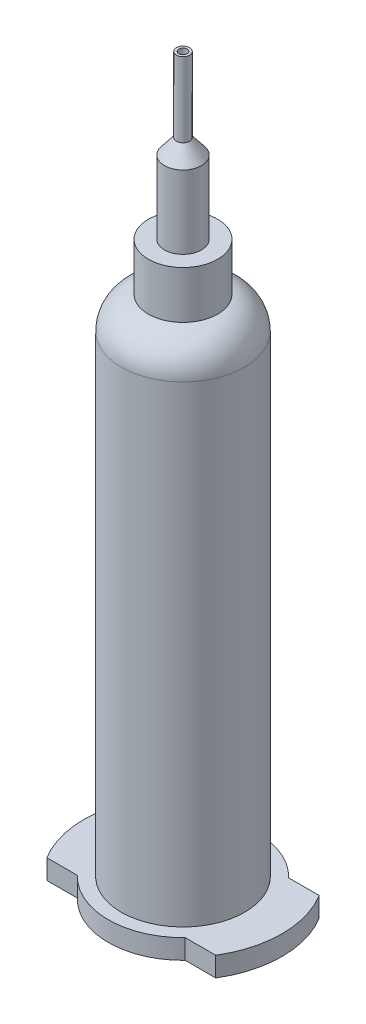
SolidWorks part; units mm, degrees
ref_plane "Front Plane" through (0, 0, 0) normal (0, 0, 1) x (1, 0, 0)
ref_plane "Top Plane" through (0, 0, 0) normal (0, 1, 0) x (1, 0, 0)
ref_plane "Right Plane" through (0, 0, 0) normal (1, 0, 0) x (0, 0, -1)
ref_axis "Axis1" through (-33.0333, 0, 0) along (1, 0, 0)
ref_axis "Axis2" through (0, 24.5224, 0) along (0, -1, 0)
ref_axis "Axis3" through (0, 0, -52.9538) along (0, 0, 1)
sketch "Sketch2" plane through (0, 0, 0) normal (0, 0, 1) x (1, 0, 0)
  line L9 (0, 54.38) -> (1, 54.38)
  line L10 (1, 54.38) -> (1, 43.03)
  line L11 (1, 43.03) -> (2.825, 40.74)
  line L12 (2.825, 40.74) -> (2.825, 29.62)
  line L13 (2.825, 29.62) -> (5.275, 29.62)
  line L14 (5.275, 29.62) -> (5.275, 22.38)
  line L15 (5.275, 22.38) -> (9.4, 22.38)
  line L16 (9.4, 22.38) -> (9.4, -54.38)
  line L17 (9.4, -54.38) -> (15.075, -54.38)
  line L18 (15.075, -54.38) -> (15.075, -57.38)
  line L19 (15.075, -57.38) -> (0, -57.38)
  line L20 (0, 54.38) -> (0, -54.38)
  line L21 (0, -54.38) -> (0, -57.38)
  line L22 (0, -54.38) -> (9.4, -54.38) construction
  point P13 (0, 0)
  point P15 (0, 0)
  dimension "D2" = 1
  dimension "D3" = 11.35
  dimension "D5" = 5.275
  dimension "D6" = 2.825
  dimension "D7" = 32
  dimension "D8" = 24.76
  dimension "D9" = 3
  dimension "D10" = 9.4
  dimension "D11" = 76.76
  dimension "D12" = 2.29
  dimension "D13" = 15.075
revolve "Revolve1" add sketch "Sketch2" angle 360 about axis through (0, 24.5224, 0) along (0, -1, 0) region at (4.5621, -13.1889, 0)
fillet "Fillet1" radius 5 1 edges at (0, 22.38, 9.4)
sketch "Sketch3" plane through (0, -54.38, 0) normal (0, 1, 0) x (1, 0, 0)
  line L0 (-12.8546, 7.875) -> (-8.2082, 7.875)
  line L1 (8.2082, 7.875) -> (12.8546, 7.875)
  line L2 (-111.883, 0) -> (111.883, 0) construction
  line L3 (-12.8546, -7.875) -> (-8.2082, -7.875)
  line L4 (8.2082, -7.875) -> (12.8546, -7.875)
  circle A0 centre (0, 0) radius 15.075 construction
  arc A1 (-8.2082, 7.875) -> (8.2082, 7.875) centre (0, 0) cw
  arc A2 (-12.8546, 7.875) -> (12.8546, 7.875) centre (0, 0) cw
  arc A3 (-8.2082, -7.875) -> (8.2082, -7.875) centre (0, 0) ccw
  arc A4 (-12.8546, -7.875) -> (12.8546, -7.875) centre (0, 0) ccw
  dimension "D2" = 11.375
  dimension "D1" = 15.75
extrude "Cut-Extrude1" cut sketch "Sketch3" against normal up to surface (3 mm away) up to face at (0, -57.38, 15.075)
sketch "Sketch4" plane through (0, -57.38, 0) normal (0, -1, 0) x (1, 0, 0)
  circle A0 centre (0, 0) radius 7.925
  dimension "D1" = 15.85
extrude "Cut-Extrude2" cut sketch "Sketch4" against normal blind 74
sketch "Sketch5" plane through (0, 54.38, 0) normal (0, 1, 0) x (1, 0, 0)
  circle A0 centre (0, 0) radius 0.6274
extrude "Cut-Extrude3" cut sketch "Sketch5" against normal blind 41
fillet "Fillet3" radius 10 1 edges at (0, 16.62, -0.6274)
ref_plane "Plane1" through (0, 16.62, 0) normal (0, 1, 0) x (1, 0, 0)
sketch "Sketch6" plane through (0, 16.62, 0) normal (0, 1, 0) x (1, 0, 0)
  circle A0 centre (0, 0) radius 7.925
  circle A1 centre (0, 0) radius 7.925 construction
extrude "Boss-Extrude2" add sketch "Sketch6" against normal blind 15 separate body
